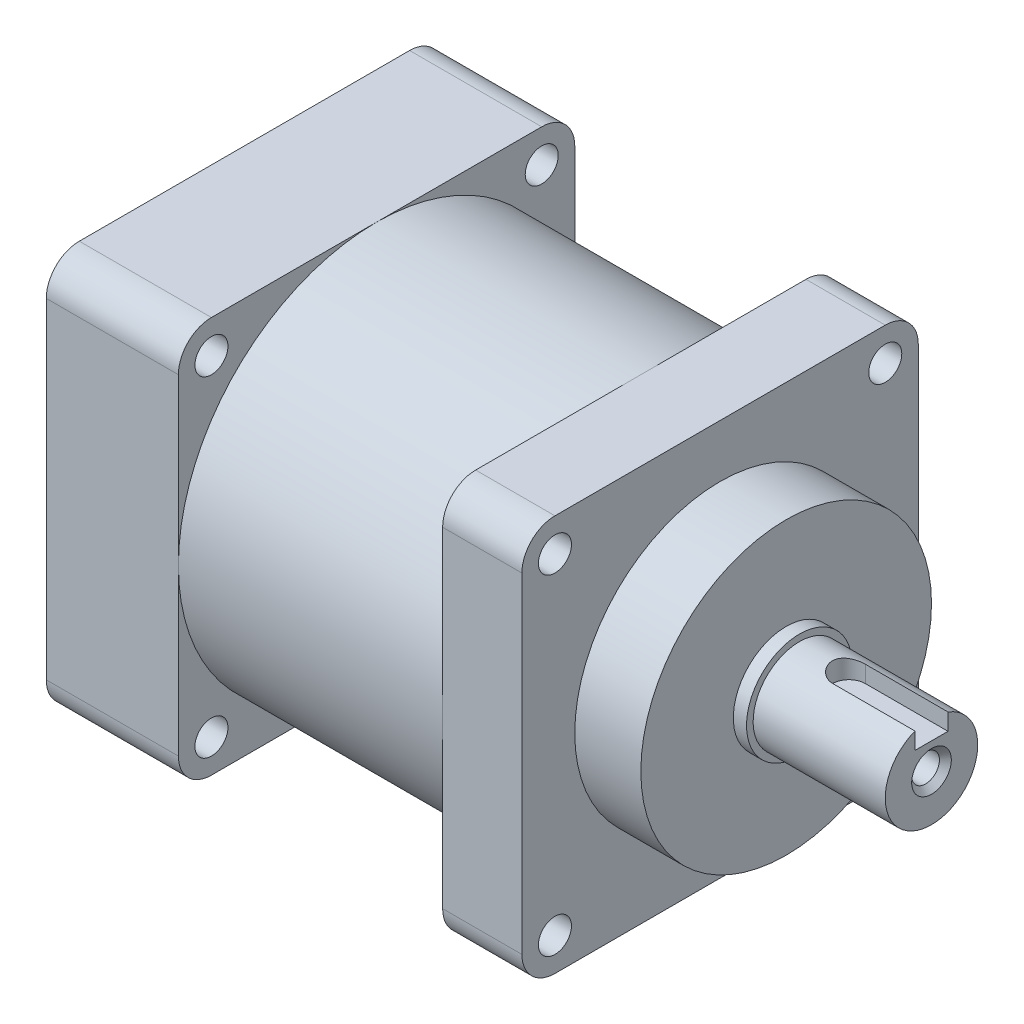
SolidWorks part; units mm, degrees
ref_plane "Спереди" through (0, 0, 0) normal (0, 0, 1) x (1, 0, 0)
ref_plane "Сверху" through (0, 0, 0) normal (0, 1, 0) x (1, 0, 0)
ref_plane "Справа" through (0, 0, 0) normal (1, 0, 0) x (0, 0, -1)
sketch "Эскиз1" plane through (0, 0, 0) normal (1, 0, 0) x (0, 0, -1)
  line L1 (0, 0) -> (60, 0)
  line L2 (0, 0) -> (0, 60)
  line L3 (0, 60) -> (60, 60)
  line L4 (60, 0) -> (60, 60)
  dimension "D1" = 60
  dimension "D2" = 60
extrude "Бобышка-Вытянуть1" add sketch "Эскиз1" along normal blind 20
sketch "Эскиз2" plane through (20, 0, 0) normal (1, 0, 0) x (0, 0, -1)
  line L0 (0, 60) -> (60, 0) construction
  circle A0 centre (30, 30) radius 30
extrude "Бобышка-Вытянуть2" add sketch "Эскиз2" along normal blind 40
sketch "Эскиз3" plane through (60, 0, 0) normal (1, 0, 0) x (0, 0, -1)
  line L1 (0, 60) -> (60, 60)
  line L2 (0, 60) -> (0, 0)
  line L3 (0, 0) -> (60, 0)
  line L4 (60, 60) -> (60, 0)
extrude "Бобышка-Вытянуть3" add sketch "Эскиз3" along normal blind 12
sketch "Эскиз4" plane through (72, 0, 0) normal (1, 0, 0) x (0, 0, -1)
  line L0 (0, 60) -> (60, 0) construction
  circle A0 centre (30, 30) radius 22
  dimension "D1" = 44
extrude "Бобышка-Вытянуть4" add sketch "Эскиз4" along normal blind 10
sketch "Эскиз5" plane through (82, 0, 0) normal (1, 0, 0) x (0, 0, -1)
  circle A0 centre (30, 30) radius 7
  dimension "D1" = 14
extrude "Бобышка-Вытянуть5" add sketch "Эскиз5" along normal blind 22
sketch "Эскиз6" plane through (0, 0, 0) normal (-1, 0, 0) x (0, 0, 1)
  line L5 (-60, 60) -> (0, 0) construction
  line L8 (0, 60) -> (-60, 0) construction
  line L9 (-55, 55) -> (-5, 55) construction
  line L10 (-5, 55) -> (-5, 5) construction
  line L11 (-5, 5) -> (-55, 5) construction
  line L12 (-55, 5) -> (-55, 55) construction
  circle A0 centre (-55, 55) radius 2.5
  circle A1 centre (-5, 55) radius 2.5
  circle A2 centre (-5, 5) radius 2.5
  circle A3 centre (-55, 5) radius 2.5
  dimension "D3" = 5
  dimension "D1" = 50
  dimension "D2" = 50
extrude "Вырез-Вытянуть1" cut sketch "Эскиз6" against normal through all
sketch "Эскиз7" plane through (0, 0, 0) normal (-1, 0, 0) x (0, 0, 1)
  line L0 (-60, 60) -> (0, 0) construction
  circle A0 centre (-30, 30) radius 25
  dimension "D1" = 50
extrude "Вырез-Вытянуть2" cut sketch "Эскиз7" against normal blind 5
sketch "Эскиз8" plane through (5, 0, 0) normal (-1, 0, 0) x (0, 0, 1)
  circle A0 centre (-30, 30) radius 7
  dimension "D1" = 14
extrude "Вырез-Вытянуть3" cut sketch "Эскиз8" against normal blind 25
sketch "Эскиз10" plane through (104, 0, 0) normal (1, 0, 0) x (0, 0, -1)
  line L0 (27.5, 34) -> (32.5, 34)
  line L1 (30, 30) -> (30, 43700.6107) construction
  line L2 (27.5, 34) -> (27.5, 36.5383)
  line L3 (32.5, 34) -> (32.5, 36.5383)
  line L4 (30, 37) -> (22.9979, 37) construction
  line L5 (-7.2981, 23) -> (-16.0172, 23) construction
  circle A2 centre (30, 30) radius 7 construction
  circle A3 centre (30, 30) radius 7 construction
  arc A4 (27.5, 36.5383) -> (32.5, 36.5383) centre (30, 30) cw
  dimension "D1" = 5
  dimension "D2" = 3
extrude "Вырез-Вытянуть5" cut sketch "Эскиз10" against normal blind 15
sketch "Эскиз11" plane through (82, 0, 0) normal (1, 0, 0) x (0, 0, -1)
  circle A0 centre (30, 30) radius 22 construction
  circle A1 centre (30, 30) radius 22 construction
  circle A2 centre (30, 30) radius 8
  dimension "D1" = 16
fillet "Скругление1" 2 edges at (89, 35.2692, -27.5) (89, 35.2692, -32.5) type full round first side face at (96.5, 35.2692, -27.5) second side face at (96.5, 35.2692, -32.5) middle face at (89, 35.3846, -30)
extrude "Бобышка-Вытянуть6" add sketch "Эскиз11" along normal blind 2
sketch "Эскиз14" plane through (104, 0, 0) normal (1, 0, 0) x (0, 0, -1)
  circle A0 centre (30, 30) radius 22 construction
  circle A1 centre (30, 30) radius 22 construction
  point P0 (30, 30)
hole_wizard "Отверстие обработанное метчиком M5x0.751" positions "Эскиз14" profile "Эскиз13" tap size "M5x0.75" standard "DIN"
cosmetic thread "Отверстие резьбы2" parameters "D1"=10, "D2"=5
sketch "Эскиз13" plane through (104, 30, -30) normal (0, 1, 0) x (0, 0, -1)
  line L0 (0, 0) -> (0, 15.2618)
  line L1 (0, 15.2618) -> (2.1, 14)
  line L2 (2.1, 14) -> (2.1, 0.9)
  line L3 (2.1, 0.9) -> (3, 0)
  line L5 (3, 0) -> (0, 0)
  line L6 (-2.1, 0.9) -> (-3, 0) construction
  line L10 (0, 15.2618) -> (-2.1, 14) construction
  line L11 (0, -6.35) -> (0, 107.95) construction
  dimension "Диаметр сверла" = 4.2
  dimension "Глубина сверла" = 14
  dimension "Диаметр передней зенковки" = 6
  dimension "Угол передней зенковки" = 90
  dimension "Угол заточки сверла" = 118
fillet "Скругление2" radius 5 8 edges at (10, 0, 0) (10, 0, -60) (10, 60, 0) (10, 60, -60) (66, 0, 0) (66, 0, -60) (66, 60, 0) (66, 60, -60)
sketch "Эскиз15" plane through (5, 0, 0) normal (-1, 0, 0) x (0, 0, 1)
  line L0 (-30, 30) -> (-30, 42.7) construction
  line L1 (-44.502, 30) -> (-34.2905, 30) construction
  line L2 (-30, 23) -> (-38.6955, 23) construction
  line L3 (-32.5, 39) -> (-27.5, 39)
  line L4 (-32.5, 39) -> (-32.5, 36.5383)
  line L5 (-32.5, 36.5383) -> (-27.5, 36.5383)
  line L6 (-27.5, 39) -> (-27.5, 36.5383)
  circle A0 centre (-30, 30) radius 7 construction
  circle A1 centre (-30, 30) radius 7 construction
  point P12 (0, 0)
  point P14 (0, 0)
  point P15 (-27.5, 33.1459)
  dimension "D1" = 16
  dimension "D2" = 5
extrude "Вырез-Вытянуть6" cut sketch "Эскиз15" against normal blind 24
fillet "Скругление3" 2 edges at (29, 37.7692, -27.5) (29, 37.7692, -32.5) type full round first side face at (17, 37.7692, -27.5) second side face at (17, 37.7692, -32.5) middle face at (29, 37.8846, -30)
